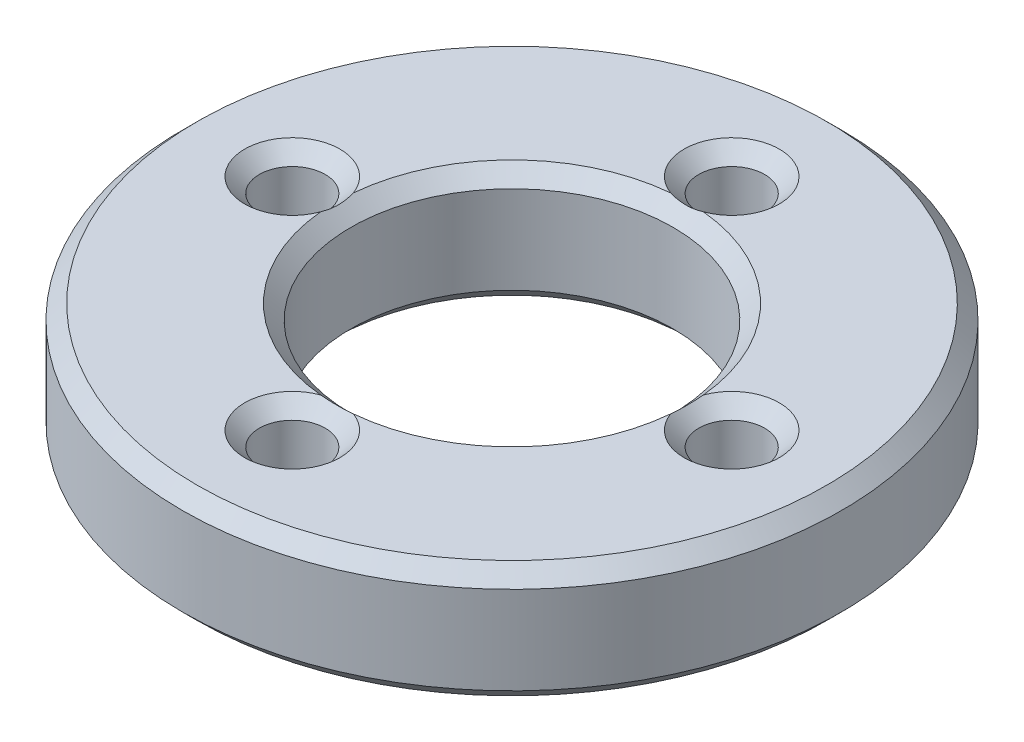
SolidWorks part; units mm, degrees
ref_plane "Front Plane" through (0, 0, 0) normal (0, 0, 1) x (1, 0, 0)
ref_plane "Top Plane" through (0, 0, 0) normal (0, 1, 0) x (1, 0, 0)
ref_plane "Right Plane" through (0, 0, 0) normal (1, 0, 0) x (0, 0, -1)
sketch "Sketch1" plane through (0, 0, 0) normal (0, 1, 0) x (1, 0, 0)
  line L0 (15, 0) -> (-15, 0) construction
  line L1 (0, 15) -> (0, -15) construction
  circle A0 centre (0, 0) radius 11
  circle A1 centre (0, 0) radius 22.5
  circle A2 centre (-15, 0) radius 2.25
  circle A3 centre (15, 0) radius 2.25
  circle A4 centre (0, -15) radius 2.25
  circle A5 centre (0, 15) radius 2.25
  point P11 (0, 0)
  point P14 (0, 0)
  dimension "28" = 45
  dimension "D2" = 22
  dimension "D5" = 4.5
  dimension "D6" = 4.5
  dimension "D7" = 4.5
  dimension "D8" = 4.5
  dimension "D3" = 30
  dimension "D4" = 30
extrude "Boss-Extrude1" add sketch "Sketch1" along normal blind 8
chamfer "Chamfer1" distance 1 angle 45 12 edges at (-15, 0, 2.25) (0, 0, -12.75) (15, 0, 2.25) (0, 0, 17.25) (0, 0, 11) (0, 0, 22.5) (-15, 8, 2.25) (15, 8, 2.25) (0, 8, 11) (0, 8, 22.5) (0, 8, 17.25) (0, 8, -12.75)
